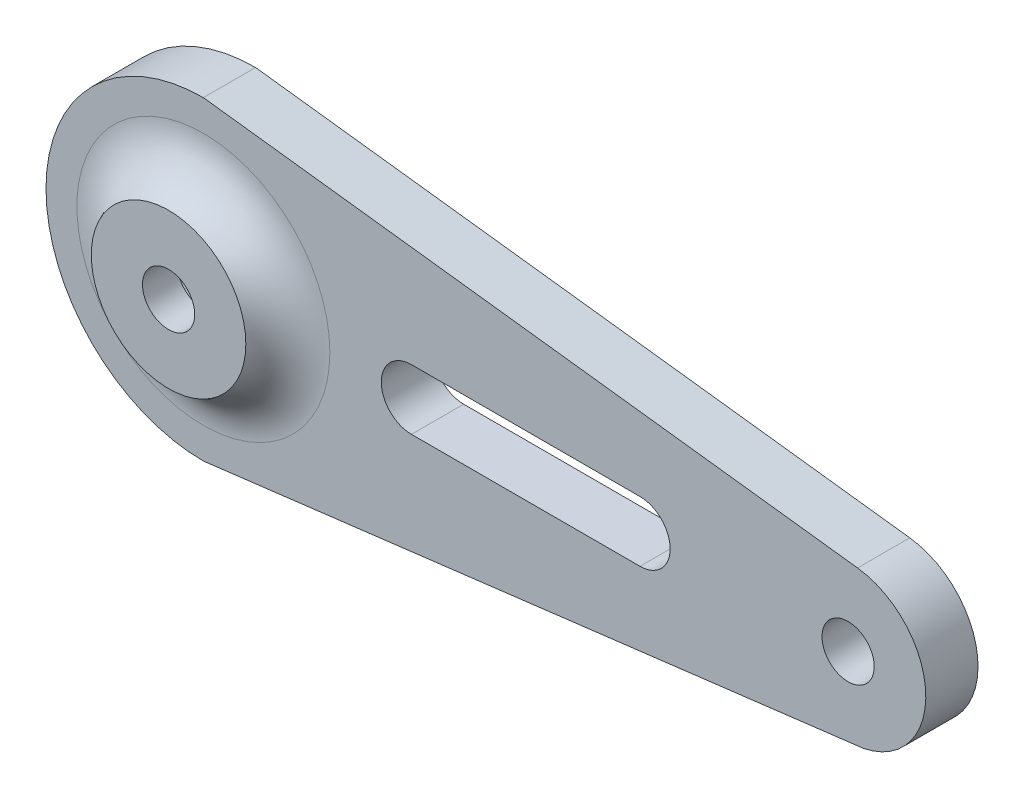
SolidWorks part; units mm, degrees
ref_plane "Front Plane" through (0, 0, 0) normal (0, 0, 1) x (1, 0, 0)
ref_plane "Top Plane" through (0, 0, 0) normal (0, 1, 0) x (1, 0, 0)
ref_plane "Right Plane" through (0, 0, 0) normal (1, 0, 0) x (0, 0, -1)
sketch "Sketch1" plane through (0, 0, 0) normal (0, 0, 1) x (1, 0, 0)
  line L0 (-70.9057, 106.8505) -> (-33.86, 106.8505) construction
  line L1 (-70.9057, 115.8929) -> (-33.3164, 111.2828)
  line L2 (-70.9057, 97.8081) -> (-32.9566, 102.4773)
  line L3 (-45.8174, 106.8505) -> (-58.9483, 106.8505) construction
  line L4 (-45.8174, 105.1159) -> (-58.9483, 105.1159)
  line L5 (-45.8174, 108.5851) -> (-58.9483, 108.5851)
  circle A0 centre (-70.9057, 106.8505) radius 3
  arc A1 (-70.9057, 115.8929) -> (-70.9057, 97.8081) centre (-70.9057, 106.8505) ccw
  circle A2 centre (-33.86, 106.8505) radius 1.5
  arc A3 (-33.6764, 102.3887) -> (-33.3164, 111.2828) centre (-33.86, 106.8505) ccw
  arc A4 (-45.8174, 105.1159) -> (-45.8174, 108.5851) centre (-45.8174, 106.8505) ccw
  arc A5 (-58.9483, 108.5851) -> (-58.9483, 105.1159) centre (-58.9483, 106.8505) ccw
  point P11 (-52.3829, 106.8505)
  dimension "D1" = 3
  dimension "D2" = 6
extrude "Boss-Extrude1" add sketch "Sketch1" along normal blind 3 contours L2 A3 L1 A1 A5 L5 A4 L4 A0 A2 region at (-52.1764, 113.055, 0)
sketch "Sketch2" plane through (0, 0, 3) normal (0, 0, 1) x (1, 0, 0)
  circle A0 centre (-70.9057, 106.8505) radius 1.5
  circle A1 centre (-70.9057, 106.8505) radius 4.4402
extrude "Boss-Extrude2" add sketch "Sketch2" along normal blind 2
fillet "Fillet1" radius 3 1 edges at (-66.4655, 106.8505, 3)
